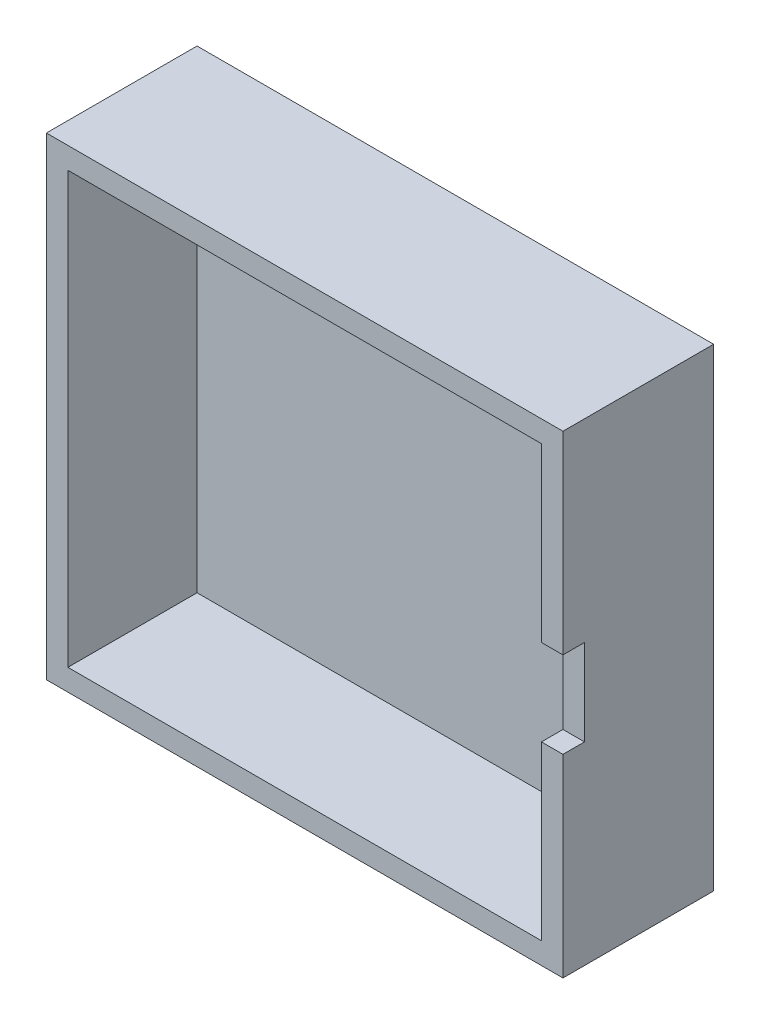
SolidWorks part; units mm, degrees
ref_plane "Plan de face" through (0, 0, 0) normal (0, 0, 1) x (1, 0, 0)
ref_plane "Plan de dessus" through (0, 0, 0) normal (0, 1, 0) x (1, 0, 0)
ref_plane "Plan de droite" through (0, 0, 0) normal (1, 0, 0) x (0, 0, -1)
sketch "Esquisse1" plane through (0, 0, 0) normal (0, 0, 1) x (1, 0, 0)
  line L0 (-10, 210) -> (230, 210)
  line L1 (0, 0) -> (220, 0)
  line L2 (0, 0) -> (0, 200)
  line L3 (0, 200) -> (220, 200)
  line L4 (220, 0) -> (220, 200)
  line L5 (230, -10) -> (230, 210)
  line L6 (-10, -10) -> (230, -10)
  line L7 (-10, -10) -> (-10, 210)
  dimension "D1" = 200
  dimension "D2" = 220
  dimension "D3" = 10
extrude "Boss.-Extru.3" add sketch "Esquisse1" along normal blind 60
extrude "Boss.-Extru.4" add sketch "Esquisse1<2>" against normal blind 10 contours L1 L4 L3 L2 | L7 L6 L5 L0 L4 L1 L2 L3 region at (110, 206.7442, 0) region at (110, 100, 0)
sketch "Esquisse1<2>" plane through (0, 0, 0) normal (0, 0, 1) x (1, 0, 0) same geometry as "Esquisse1"
sketch "Esquisse4" plane through (220, 0, 0) normal (-1, 0, 0) x (0, 0, 1)
  line L0 (60, 100) -> (60, 120) construction
  line L1 (60, 0) -> (60, 200) construction
  line L2 (60, 120) -> (50, 120)
  line L3 (50, 120) -> (50, 80)
  line L4 (50, 80) -> (60, 80)
  dimension "D1" = 20
  dimension "D2" = 10
  dimension "D3" = 40
extrude "Enlèv. mat.-Extru.17" cut sketch "Esquisse4" against normal through all
